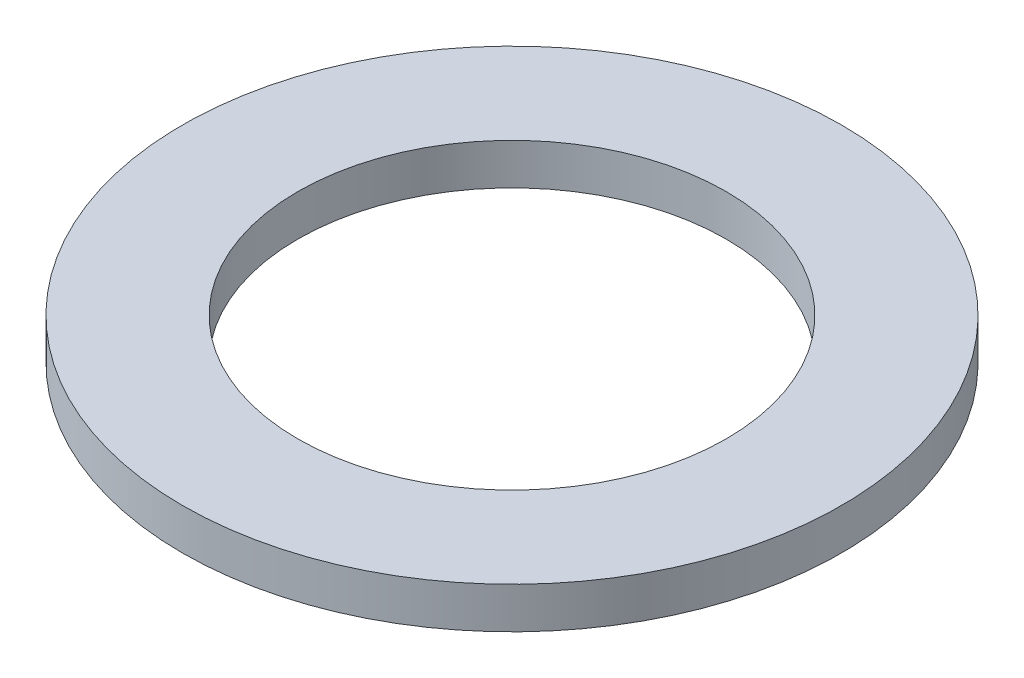
SolidWorks part; units mm, degrees
ref_plane "Спереди" through (0, 0, 0) normal (0, 0, 1) x (1, 0, 0)
ref_plane "Сверху" through (0, 0, 0) normal (0, 1, 0) x (1, 0, 0)
ref_plane "Справа" through (0, 0, 0) normal (1, 0, 0) x (0, 0, -1)
sketch "Эскиз1" plane through (0, 0, 0) normal (0, 1, 0) x (1, 0, 0)
  circle A0 centre (0, 0) radius 4
  circle A1 centre (0, 0) radius 2.6
  point P5 (0, 0)
extrude "Бобышка-Вытянуть1" add sketch "Эскиз1" along normal blind 0.5
